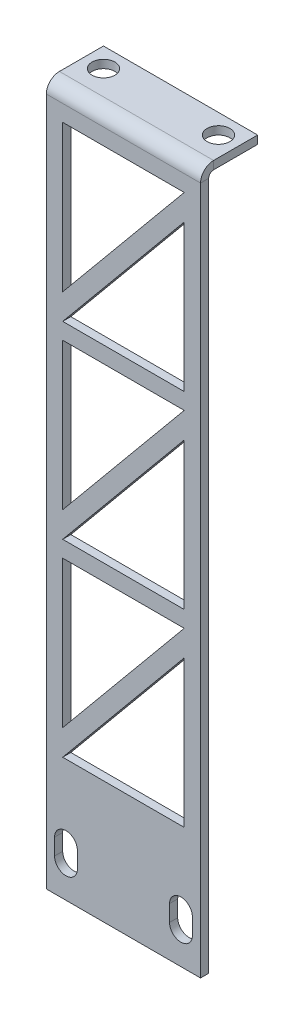
SolidWorks part; units mm, degrees
note: The reader was unsure of these and kept them because the rebuilt part matched: flange length of "Edge-Flange1".
ref_plane "Front Plane" through (0, 0, 0) normal (0, 0, 1) x (1, 0, 0)
ref_plane "Top Plane" through (0, 0, 0) normal (0, 1, 0) x (1, 0, 0)
ref_plane "Right Plane" through (0, 0, 0) normal (1, 0, 0) x (0, 0, -1)
sketch "Sketch1" plane through (0, 0, 0) normal (0, 0, 1) x (1, 0, 0)
  line L0 (-7.05, -36.5) -> (-7.05, -38.5) construction
  line L1 (-9.45, -42.5) -> (9.45, -42.5)
  line L2 (-9.45, -42.5) -> (-9.45, 42.5)
  line L3 (-9.45, 42.5) -> (9.45, 42.5)
  line L4 (9.45, -42.5) -> (9.45, 42.5)
  line L5 (-9.45, -42.5) -> (9.45, 42.5) construction
  line L6 (-9.45, 42.5) -> (9.45, -42.5) construction
  line L7 (-5.65, -36.5) -> (-5.65, -38.5)
  line L8 (-8.45, -36.5) -> (-8.45, -38.5)
  line L9 (7.05, -36.5) -> (7.05, -38.5) construction
  line L10 (8.45, -36.5) -> (8.45, -38.5)
  line L11 (5.65, -36.5) -> (5.65, -38.5)
  arc A0 (-5.65, -36.5) -> (-8.45, -36.5) centre (-7.05, -36.5) ccw
  arc A1 (-8.45, -38.5) -> (-5.65, -38.5) centre (-7.05, -38.5) ccw
  arc A2 (8.45, -36.5) -> (5.65, -36.5) centre (7.05, -36.5) ccw
  arc A3 (5.65, -38.5) -> (8.45, -38.5) centre (7.05, -38.5) ccw
  point P0 (0, 0)
  point P8 (-7.05, -37.5)
  point P14 (7.05, -37.5)
  dimension "D1" = 85
  dimension "D2" = 18.9
  dimension "D3" = 2.8
  dimension "D4" = 2
  dimension "D5" = 2.8
  dimension "D6" = 2
  dimension "D7" = 5
  dimension "D8" = 5
  dimension "D9" = 2.4
  dimension "D10" = 2.4
base flange "Base-Flange1" sketch "Sketch1" thickness 1 reverse thickness direction no parameters "D1"=0.6
edge flange "Edge-Flange1" sketch "Sketch8" flange angle 90 flange length 6 flange position material outside bend radius 0.6 thickness 1 relief rectangular parameters "D6"=10
sketch "Sketch8" plane through (0, 42.5, -1) normal (0, 1, 0) x (1, 0, 0)
  line L2 (-9.45, 0) -> (-9.45, 6)
  line L3 (-9.45, 6) -> (9.45, 6)
  line L4 (9.45, 6) -> (9.45, 0)
  line L5 (9.45, 0) -> (-9.45, 0) construction
  line L6 (9.45, 0) -> (-9.45, 0)
bend "EdgeBend1" bend radius 0.6 bend angle 90 parameters "D5"=1
sketch "Sketch9" plane through (0, 43.5, 0) normal (0, 1, 0) x (1, 0, 0)
  line L0 (-9.45, 7) -> (-9.45, 1.6) construction
  line L1 (9.45, 7) -> (-9.45, 7) construction
  line L2 (9.45, 1.6) -> (9.45, 7) construction
  circle A0 centre (-7.05, 4.6) radius 1.4
  circle A1 centre (7.05, 4.6) radius 1.4
  dimension "D1" = 2.8
  dimension "D2" = 2.8
  dimension "D3" = 2.4
  dimension "D4" = 2.4
  dimension "D5" = 2.4
  dimension "D6" = 2.4
extrude "Cut-Extrude1" cut sketch "Sketch9" against normal blind 10 normal cut yes
sketch "Sketch12" plane through (0, 0, 0) normal (0, 0, 1) x (1, 0, 0)
  line L0 (7.45, 39.9) -> (-7.45, 21.9)
  line L1 (-7.45, 21.9) -> (-7.45, 39.9)
  line L2 (-7.45, 39.9) -> (7.45, 39.9)
  line L3 (7.45, 36.7635) -> (-7.45, 18.7635)
  line L4 (-7.45, 18.7635) -> (7.45, 18.7635)
  line L5 (7.45, 18.7635) -> (7.45, 36.7635)
  line L6 (-7.45, 16.7635) -> (7.45, 16.7635)
  line L7 (7.45, 16.7635) -> (-7.45, -1.2365)
  line L8 (-7.45, -1.2365) -> (-7.45, 16.7635)
  line L9 (7.45, 13.627) -> (-7.45, -4.373)
  line L10 (-7.45, -4.373) -> (7.45, -4.373)
  line L11 (7.45, -4.373) -> (7.45, 13.627)
  line L12 (-7.45, -6.373) -> (7.45, -6.373)
  line L13 (7.45, -6.373) -> (-7.45, -24.373)
  line L14 (-7.45, -24.373) -> (-7.45, -6.373)
  line L15 (-7.45, -27.5095) -> (7.45, -9.5095)
  line L16 (7.45, -9.5095) -> (7.45, -27.5095)
  line L17 (7.45, -27.5095) -> (-7.45, -27.5095)
  line L18 (9.45, 41.9) -> (-9.45, 41.9) construction
  line L19 (-9.45, 41.9) -> (-9.45, -42.5) construction
  line L20 (9.45, -42.5) -> (9.45, 41.9) construction
  dimension "D1" = 2
  dimension "D2" = 2
  dimension "D3" = 2
  dimension "D4" = 2
  dimension "D5" = 2
  dimension "D6" = 2
  dimension "D7" = 2
  dimension "D8" = 2
  dimension "D9" = 2
  dimension "D10" = 2
  dimension "D11" = 2
  dimension "D12" = 2
  dimension "D13" = 2
  dimension "D14" = 2
  dimension "D15" = 2
  dimension "D16" = 2
  dimension "D17" = 18
  dimension "D18" = 18
  dimension "D19" = 18
  dimension "D20" = 2
extrude "Cut-Extrude4" cut sketch "Sketch12" against normal blind 10 normal cut yes
sketch "Bend-Lines1" [suppressed] plane through (0, 0, 0) normal (0, 1, 0) x (1, 0, 0)
sketch "Bounding-Box1" [suppressed] plane through (0, 0, 0) normal (0, 1, 0) x (1, 0, 0)
fillet "Fillet1" [suppressed] radius 1
fillet "Fillet2" [suppressed] radius 2
sheet metal parameters "Sheet-Metal(1)" thickness 1 parameters "D1"=0.6
flat pattern "Flat-Pattern(1)" [suppressed]
sketch "Bend-Lines2" plane through (0, 0, 0) normal (0, 1, 0) x (1, 0, 0)
sketch "Bounding-Box2" [suppressed] plane through (0, 0, 0) normal (0, 1, 0) x (1, 0, 0)
sheet metal parameters "Sheet-Metal(2)" thickness 1 parameters "D1"=0.6
flat pattern "Flat-Pattern(1)" [suppressed]
sketch "Bend-Lines2" plane through (0, 0, 0) normal (0, 1, 0) x (1, 0, 0)
sketch "Bounding-Box2" [suppressed] plane through (0, 0, 0) normal (0, 1, 0) x (1, 0, 0)
bend of the flat pattern "Flatten-<EdgeBend1>1"
sheet metal parameters "Sheet-Metal(3)" thickness 1 parameters "D1"=0.6
flat pattern "Flat-Pattern(1)" [suppressed]
sketch "Bend-Lines2" plane through (0, 0, 0) normal (0, 1, 0) x (1, 0, 0)
sketch "Bounding-Box2" [suppressed] plane through (0, 0, 0) normal (0, 1, 0) x (1, 0, 0)
bend of the flat pattern "Flatten-<EdgeBend1>1"
sheet metal parameters "Sheet-Metal(6)" thickness 1 parameters "D1"=0.6
flat pattern "Flat-Pattern(1)"
sketch "Bend-Lines2" plane through (0, 0, 0) normal (0, 0, 1) x (1, 0, 0)
  line L0 (9.45, 42.7639) -> (-9.45, 42.7639) construction
  line L1 (9.45, 42.7639) -> (-9.45, 42.7639) construction
sketch3d "Bounding-Box2" [suppressed]
  line L0 (9.45, 49.0279, 0) -> (9.45, -42.5, 0) construction
  line L1 (-9.45, 49.0279, 0) -> (-9.45, -42.5, 0) construction
  line L2 (9.45, 49.0279, 0) -> (-9.45, 49.0279, 0) construction
  line L3 (9.45, -42.5, 0) -> (-9.45, -42.5, 0) construction
bend of the flat pattern "Flatten-<EdgeBend1>1"
